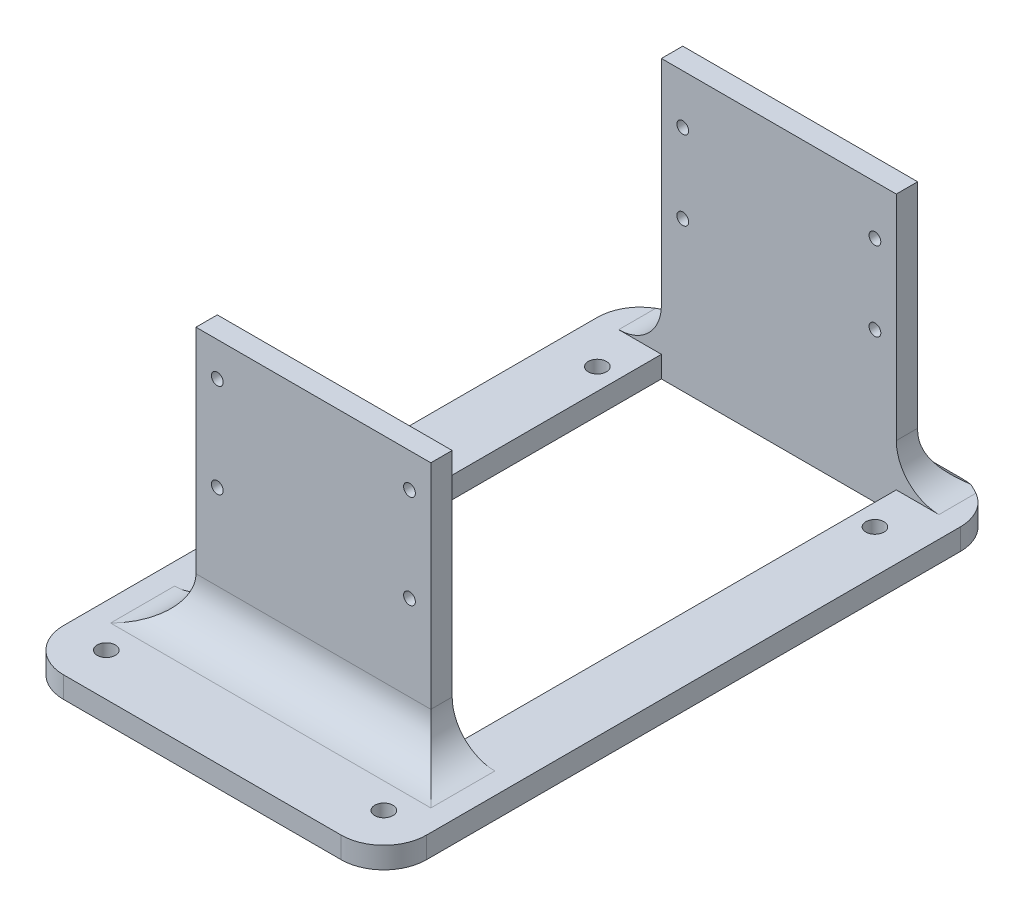
SolidWorks part; units mm, degrees
other "Markup1"
sketch "Sketch7" plane through (-69.5, 3, -80) normal (0, 1, 0) x (1, 0, 0)
sketch "Sketch8" plane through (-69.5, 5, -80) normal (0, 1, 0) x (1, 0, 0)
other "Markup2"
sketch "Sketch17" plane through (60, 65, 65) normal (0.6864, 0.6858, 0.2418) x (0.2362, 0.1043, -0.9661)
ref_plane "Front Plane" through (0, 0, 0) normal (0, 0, 1) x (1, 0, 0)
ref_plane "Top Plane" through (0, 0, 0) normal (0, 1, 0) x (1, 0, 0)
ref_plane "Right Plane" through (0, 0, 0) normal (1, 0, 0) x (0, 0, -1)
sketch "Sketch1" plane through (0, 0, 0) normal (0, 1, 0) x (1, 0, 0)
  line L1 (-42.5, 65) -> (42.5, 65)
  line L2 (-42.5, 65) -> (-42.5, -65)
  line L3 (-42.5, -65) -> (42.5, -65)
  line L4 (42.5, 65) -> (42.5, -65)
  line L5 (-42.5, 65) -> (42.5, -65) construction
  line L6 (-42.5, -65) -> (42.5, 65) construction
  point P0 (0, 0)
  dimension "D1" = 130
  dimension "D2" = 85
extrude "Boss-Extrude1" add sketch "Sketch1" along normal blind 5
sketch "Sketch10" plane through (0, 5, 0) normal (0, 1, 0) x (1, 0, 0)
  line L0 (-42.5, 65) -> (42.5, 65)
  line L1 (-42.5, 65) -> (-42.5, 80)
  line L2 (42.5, 65) -> (42.5, 80)
  line L3 (-42.5, 80) -> (42.5, 80)
  line L4 (42.5, 65) -> (-42.5, 65) construction
  line L5 (-42.5, 65) -> (-42.5, -65) construction
  line L6 (42.5, -65) -> (42.5, 65) construction
  dimension "D1" = 0
  dimension "D2" = 0
  dimension "D3" = 15
extrude "Boss-Extrude2" add sketch "Sketch10" against normal up to surface (5 mm away) up to face at (0, 0, 0)
sketch "Sketch9" plane through (0, 5, 0) normal (0, 1, 0) x (1, 0, 0)
  line L0 (0, -55) -> (0, 55) construction
  line L1 (-27.5, -34) -> (27.5, -34)
  line L2 (-27.5, -34) -> (-27.5, 70)
  line L3 (-27.5, 70) -> (27.5, 70)
  line L4 (27.5, -34) -> (27.5, 70)
  line L5 (-27.5, -34) -> (27.5, 70) construction
  line L6 (-27.5, 70) -> (27.5, -34) construction
  line L8 (42.5, 80) -> (-42.5, 80) construction
  point P0 (0, 18)
  dimension "D1" = 10
  dimension "D2" = 104
  dimension "D3" = 55
extrude "Cut-Extrude5" cut sketch "Sketch9" against normal through all
sketch "Sketch11" plane through (0, 5, 0) normal (0, 1, 0) x (1, 0, 0)
  line L0 (-27.5, 70) -> (27.5, 70)
  line L1 (-27.5, 70) -> (-27.5, 75)
  line L2 (27.5, 70) -> (27.5, 75)
  line L3 (-27.5, 75) -> (27.5, 75)
  line L4 (-27.5, -34) -> (27.5, -34)
  line L5 (-27.5, -34) -> (-27.5, -39)
  line L6 (27.5, -34) -> (27.5, -39)
  line L7 (-27.5, -39) -> (27.5, -39)
  dimension "D1" = 5
  dimension "D2" = 5
extrude "Boss-Extrude3" add sketch "Sketch11" along normal blind 60
sketch "Sketch12" plane through (0, 0, 39) normal (0, 0, 1) x (1, 0, 0)
  line L0 (-27.5, 5) -> (27.5, 5) construction
  line L1 (0, -55) -> (0, 55) construction
  circle A0 centre (-22.5, 35) radius 1.375
  circle A2 centre (22.5, 35) radius 1.375
  dimension "D3" = 2.75
  dimension "D1" = 30
  dimension "D2" = 22.5
extrude "Cut-Extrude6" cut sketch "Sketch12" against normal through all
sketch "Sketch13" plane through (0, 0, 39) normal (0, 0, 1) x (1, 0, 0)
  line L0 (0, -55) -> (0, 55) construction
  circle A0 centre (-22.5, 57) radius 1.375
  circle A1 centre (-22.5, 35) radius 1.375 construction
  circle A2 centre (22.5, 57) radius 1.375
  dimension "D2" = 2.75
  dimension "D1" = 22.5
  dimension "D3" = 22
extrude "Cut-Extrude7" cut sketch "Sketch13" against normal up to next
sketch "Sketch14" plane through (0, 0, -75) normal (0, 0, -1) x (-1, 0, 0)
  line L0 (-22.5, 35) -> (-22.5, 57.1524) construction
  line L1 (0, 55) -> (0, -55) construction
  circle A0 centre (-22.5, 53.5) radius 1.375
  circle A1 centre (22.5, 53.5) radius 1.375
  dimension "D2" = 2.75
  dimension "D1" = 18.5
extrude "Cut-Extrude8" cut sketch "Sketch14" against normal up to next
fillet "Fillet1" radius 10 1 edges at (0, 5, 39)
fillet "Fillet2" radius 10 1 edges at (0, 5, -75)
fillet "Fillet3" radius 10 4 edges at (27.5, 5, -75) (27.5, 5, 41.5) (-27.5, 5, 41.5) (-27.5, 5, -75)
sketch "Sketch16" plane through (0, 5, 0) normal (0, 1, 0) x (1, 0, 0)
  line L0 (-37.5, 80) -> (-42.5, 80) construction
  line L1 (-42.5, 80) -> (-42.5, -65) construction
  line L2 (-42.5, -65) -> (42.5, -65) construction
  line L3 (42.5, -65) -> (42.5, 80) construction
  circle A0 centre (-32.5, 60) radius 2.125
  circle A1 centre (-32.5, -55) radius 2.125
  circle A2 centre (32.5, -55) radius 2.125
  circle A3 centre (32.5, 60) radius 2.125
  dimension "D1" = 4.25
  dimension "D2" = 4.25
  dimension "D3" = 4.25
  dimension "D4" = 4.25
  dimension "D5" = 20
  dimension "D6" = 10
  dimension "D7" = 10
  dimension "D8" = 10
extrude "Cut-Extrude9" cut sketch "Sketch16" against normal blind 10
fillet "Fillet4" radius 10 4 edges at (-42.5, 2.5, -80) (42.5, 2.5, -80) (-42.5, 2.5, 65) (42.5, 2.5, 65)
